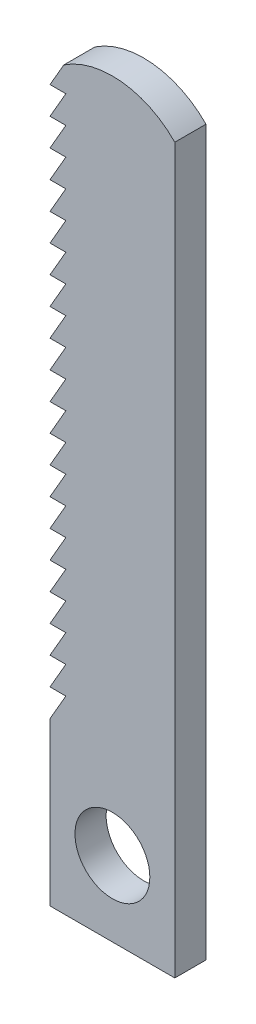
SolidWorks part; units mm, degrees
note: '?' marks a value the reader was unsure of.
ref_plane "Plan1" through (0, 0, 0) normal (0, 0, 1) x (1, 0, 0)
ref_plane "Plan2" through (0, 0, 0) normal (0, 1, 0) x (1, 0, 0)
ref_plane "Plan3" through (0, 0, 0) normal (1, 0, 0) x (0, 0, -1)
sketch "Esquisse1" plane through (0, 0, 0) normal (0, 0, 1) x (1, 0, 0)
  line L0 (0, 0) -> (0, 94.202) construction
  line L1 (-5, 99.101) -> (-5, 41.101)
  line L2 (5, 99.101) -> (5, 41.101)
  line L3 (-5, 41.101) -> (5, 41.101)
  arc A0 (5, 99.101) -> (-5, 99.101) centre (0, 94.202) ccw
  circle A1 centre (0, 47.101) radius 3
  dimension "D3" = 6
  dimension "D5" = 7
  dimension "D1" = 10
  dimension "D2" = 58
  dimension "D4" = 6
extrude "Base-Extrusion" add sketch "Esquisse1" along normal blind 2.5
sketch "Esquisse2" plane through (0, 0, 2.5) normal (0, 0, 1) x (1, 0, 0)
  line L0 (-10, 54.101) -> (20, 54.101) construction
  line L2 (-5, 41.101) -> (5, 41.101) construction
  line L3 (0, 94.202) -> (0, 40) construction
  line L4 (-5, 99.101) -> (-5, 41.101) construction
  line L5 (-5, 54.101) -> (-3.7298, 56.301)
  line L6 (-3.7298, 56.301) -> (-5, 56.301)
  dimension "D1" = 1.2702
  dimension "D2" = 13
  dimension "D4" = 2.2
  dimension "D5" = 60
extrude "Enlèv. mat.-Extru.1" cut sketch "Esquisse2" against normal through all
pattern_linear "Répétition linéaire1" count 22 spacing 2.2
ref_axis "Axe1" through (0, 47.101, 2.5) along (0, 0, -1)?
